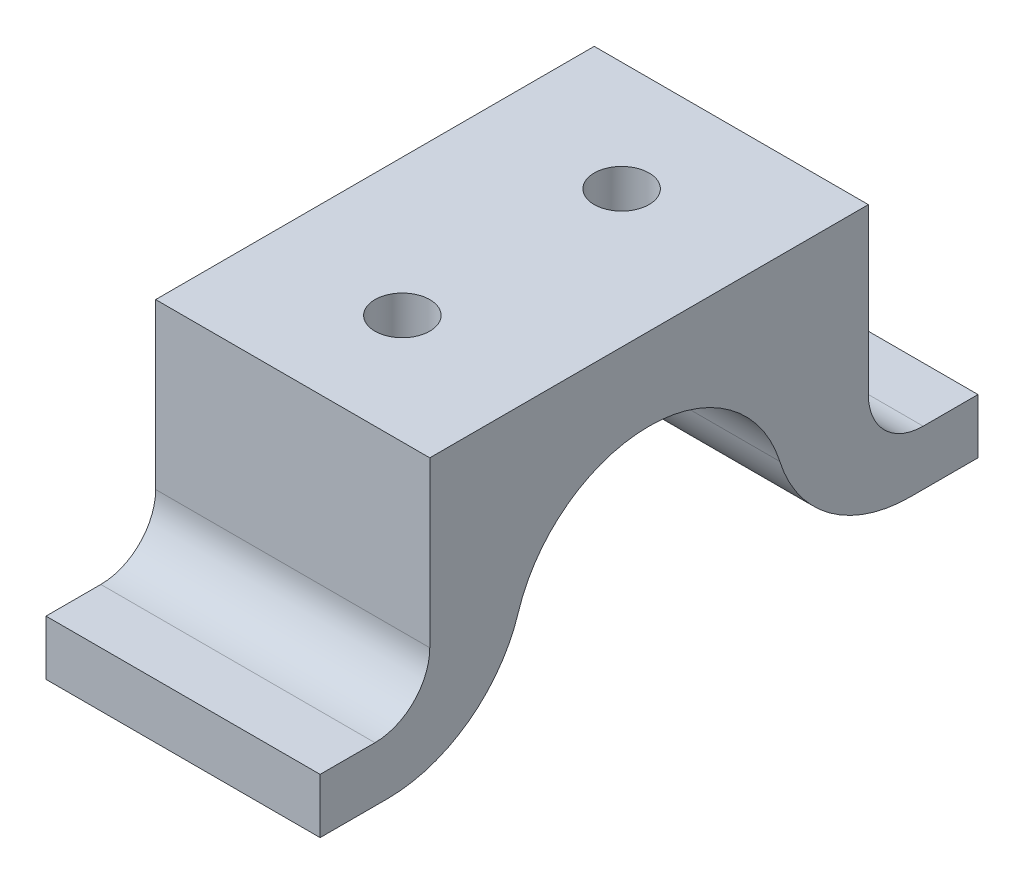
SolidWorks part; units mm, degrees
ref_plane "Front Plane" through (0, 0, 0) normal (0, 0, 1) x (1, 0, 0)
ref_plane "Top Plane" through (0, 0, 0) normal (0, 1, 0) x (1, 0, 0)
ref_plane "Right Plane" through (0, 0, 0) normal (1, 0, 0) x (0, 0, -1)
sketch "Sketch1" plane through (0, 25, 0) normal (0, -1, 0) x (1, 0, 0)
  line L0 (6.5, -6) -> (-6.5, -6) construction
  line L1 (5, -5.5) -> (-5, -5.5)
  line L2 (5, -5.5) -> (5, 10.5)
  line L3 (5, 10.5) -> (-5, 10.5)
  line L4 (-5, -5.5) -> (-5, 10.5)
  circle A2 centre (0, 6.5) radius 1 construction
  circle A3 centre (0, -1.5) radius 1 construction
  circle A4 centre (0, -1.5) radius 1.5 construction
  circle A5 centre (0, 6.5) radius 1.5 construction
  point P4 (7.0854, -5.5421)
  point P5 (0, -5.5)
  point P6 (0, 0)
  point P8 (-3.5, -5.5)
  point P9 (0, 0)
  dimension "D4" = 2
  dimension "D1" = 16
  dimension "D2" = 10
  dimension "D3" = 0.5
extrude "Boss-Extrude1" add sketch "Sketch1" along normal blind 3
sketch "Sketch2" plane through (0, 22, 0) normal (0, -1, 0) x (1, 0, 0)
  line L0 (5, -5.5) -> (5, 10.5) construction
  line L1 (-5, -5.5) -> (5, -5.5)
  line L2 (-5, -5.5) -> (-5, -2.5)
  line L3 (-5, -2.5) -> (5, -2.5)
  line L4 (5, -5.5) -> (5, -2.5)
  line L6 (-5, 10.5) -> (5, 10.5)
  line L7 (-5, 10.5) -> (-5, 7.5)
  line L8 (-5, 7.5) -> (5, 7.5)
  line L9 (5, 10.5) -> (5, 7.5)
  dimension "D1" = 3
extrude "Boss-Extrude2" add sketch "Sketch2" along normal blind 5
sketch "Sketch3" plane through (0, 17, 0) normal (0, -1, 0) x (1, 0, 0)
  line L2 (-5, 7.5) -> (5, 7.5)
  line L3 (-5, 7.5) -> (-5, 14.5)
  line L4 (-5, 14.5) -> (5, 14.5)
  line L5 (5, 7.5) -> (5, 14.5)
  line L6 (-5, -2.5) -> (5, -2.5)
  line L7 (-5, -2.5) -> (-5, -9.5)
  line L8 (-5, -9.5) -> (5, -9.5)
  line L9 (5, -2.5) -> (5, -9.5)
  point P11 (5, -2.5)
  dimension "D1" = 7
extrude "Boss-Extrude3" add sketch "Sketch3" along normal blind 2
fillet "Fillet1" radius 5 2 edges at (0, 22, 7.5) (0, 22, -2.5)
fillet "Fillet2" radius 5 2 edges at (0, 15, -2.5) (0, 15, 7.5)
fillet "Fillet3" radius 2 2 edges at (0, 17, -5.5) (0, 17, 10.5)
sketch "Sketch4" plane through (0, 25, 0) normal (0, 1, 0) x (1, 0, 0)
  circle A0 centre (0, 1.5) radius 1 construction
  circle A1 centre (0, -6.5) radius 1 construction
  circle A2 centre (0, 1.5) radius 1
  circle A3 centre (0, -6.5) radius 1
extrude "Cut-Extrude1" cut sketch "Sketch4" against normal through all
